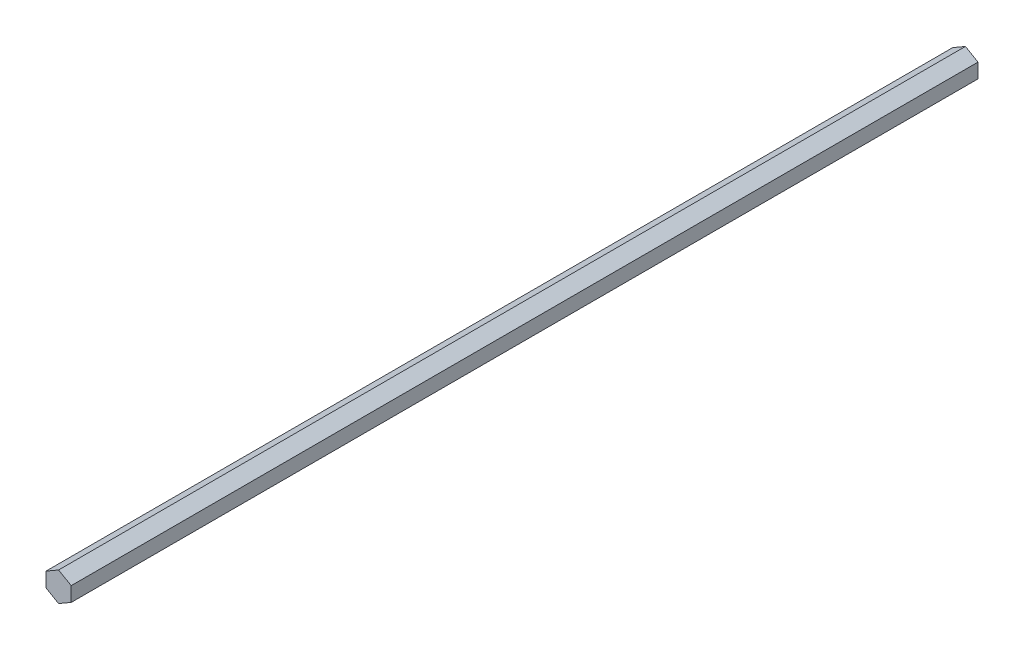
SolidWorks part; units mm, degrees
ref_plane "Front Plane" through (0, 0, 0) normal (0, 0, 1) x (1, 0, 0)
ref_plane "Top Plane" through (0, 0, 0) normal (0, 1, 0) x (1, 0, 0)
ref_plane "Right Plane" through (0, 0, 0) normal (1, 0, 0) x (0, 0, -1)
sketch "Sketch1" plane through (0, 0, 0) normal (0, 0, 1) x (1, 0, 0)
  line L1 (6.35, 3.6662) -> (0, 7.3323)
  line L2 (0, 7.3323) -> (-6.35, 3.6662)
  line L3 (-6.35, 3.6662) -> (-6.35, -3.6662)
  line L4 (-6.35, -3.6662) -> (0, -7.3323)
  line L5 (0, -7.3323) -> (6.35, -3.6662)
  line L6 (6.35, -3.6662) -> (6.35, 3.6662)
  circle A0 centre (0, 0) radius 6.35 construction
  circle A1 centre (0, 0) radius 7.3323
  dimension "D1" = 12.7
extrude "Boss-Extrude1" add sketch "Sketch1" along normal mid plane 457.2 contours L1 L2 L3 L4 L5 L6
sketch "Sketch3" plane through (0, 0, 0) normal (0, 0, 1) x (1, 0, 0)
  point P0 (0, 0)
ref_axis "Axis1" through (0, 0, 0) along (0, 0, 1)
